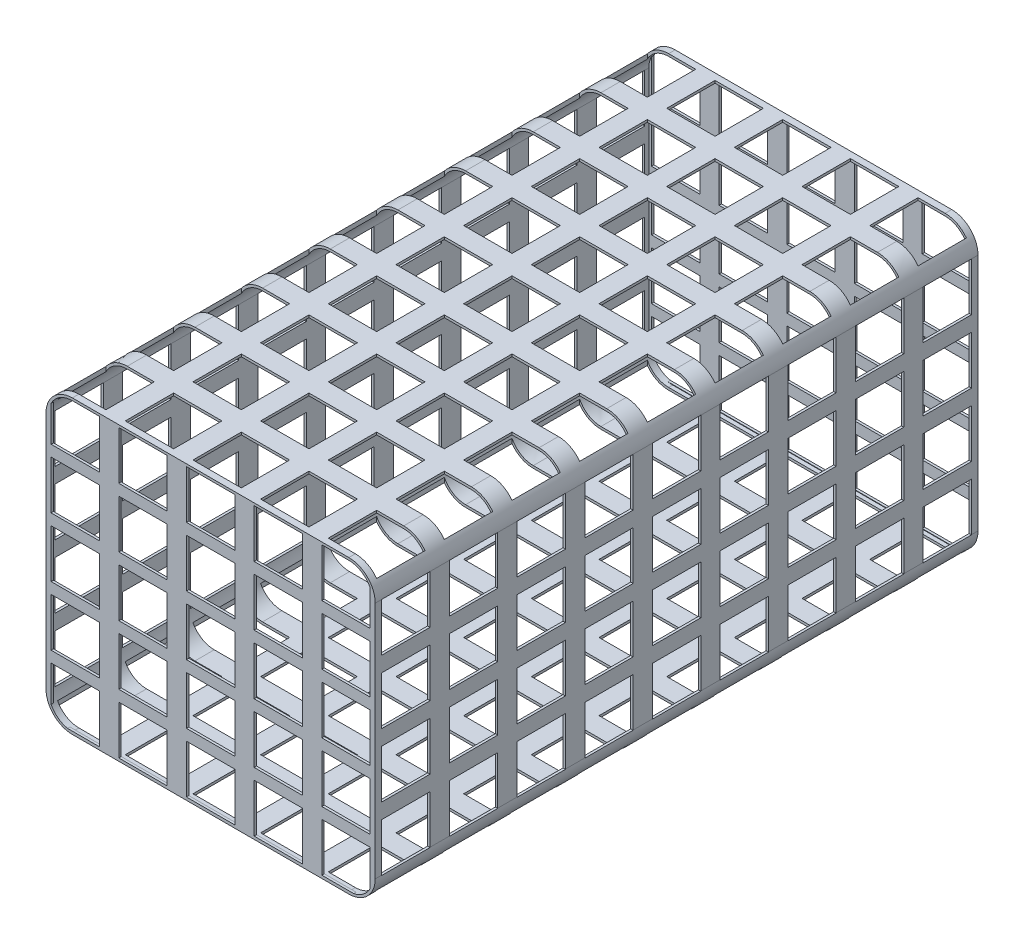
SolidWorks part; units mm, degrees
ref_plane "Front Plane" through (0, 0, 0) normal (0, 0, 1) x (1, 0, 0)
ref_plane "Top Plane" through (0, 0, 0) normal (0, 1, 0) x (1, 0, 0)
ref_plane "Right Plane" through (0, 0, 0) normal (1, 0, 0) x (0, 0, -1)
sketch "Sketch1" plane through (0, 0, 0) normal (0, 0, 1) x (1, 0, 0)
  line L0 (-72.644, 77.851) -> (72.644, 77.851)
  line L1 (-72.644, -76.581) -> (72.644, -76.581)
  line L2 (-86.487, -62.738) -> (-86.487, 62.738)
  line L3 (-72.644, 76.581) -> (72.644, 76.581)
  line L4 (86.487, -62.738) -> (86.487, 62.738)
  line L5 (-86.487, -76.581) -> (86.487, 76.581) construction
  line L6 (-86.487, 76.581) -> (86.487, -76.581) construction
  line L7 (87.757, -62.738) -> (87.757, 62.738)
  line L8 (-72.644, -77.851) -> (72.644, -77.851)
  line L9 (-87.757, -62.738) -> (-87.757, 62.738)
  arc A0 (86.487, 62.738) -> (72.644, 76.581) centre (72.644, 62.738) ccw
  arc A1 (86.487, -62.738) -> (72.644, -76.581) centre (72.644, -62.738) cw
  arc A2 (-72.644, -76.581) -> (-86.487, -62.738) centre (-72.644, -62.738) cw
  arc A3 (-86.487, 62.738) -> (-72.644, 76.581) centre (-72.644, 62.738) cw
  arc A4 (87.757, 62.738) -> (72.644, 77.851) centre (72.644, 62.738) ccw
  arc A5 (87.757, -62.738) -> (72.644, -77.851) centre (72.644, -62.738) cw
  arc A6 (-72.644, -77.851) -> (-87.757, -62.738) centre (-72.644, -62.738) cw
  arc A7 (-87.757, 62.738) -> (-72.644, 77.851) centre (-72.644, 62.738) cw
  point P0 (0, 0)
  dimension "D3" = 13.843
  dimension "D1" = 172.974
  dimension "D2" = 153.162
  dimension "D4" = 1.27
extrude "Boss-Extrude2" add sketch "Sketch1" along normal mid plane 316.738 contours A3 L2 A2 L1 A1 L4 A0 L3 | A3 L2 A2 L1 A1 L4 A0 L3 region at (0, 0, 0)
shell "Shell1" thickness 1.27
sketch "Sketch4" plane through (0, 76.581, 0) normal (0, 1, 0) x (1, 0, 0)
  line L0 (48.26, -12.7) -> (48.26, 12.7)
  line L1 (12.7, -12.7) -> (-12.7, -12.7)
  line L2 (12.7, -12.7) -> (12.7, 12.7)
  line L3 (12.7, 12.7) -> (-12.7, 12.7)
  line L4 (-12.7, -12.7) -> (-12.7, 12.7)
  line L5 (12.7, -12.7) -> (-12.7, 12.7) construction
  line L6 (12.7, 12.7) -> (-12.7, -12.7) construction
  line L7 (48.26, -12.7) -> (22.86, -12.7)
  line L8 (22.86, -12.7) -> (22.86, 12.7)
  line L9 (48.26, 12.7) -> (22.86, 12.7)
  line L10 (83.82, -12.7) -> (83.82, 12.7)
  line L11 (83.82, -12.7) -> (58.42, -12.7)
  line L12 (58.42, -12.7) -> (58.42, 12.7)
  line L13 (83.82, 12.7) -> (58.42, 12.7)
  line L14 (48.26, -48.26) -> (48.26, -22.86)
  line L15 (48.26, -48.26) -> (22.86, -48.26)
  line L16 (22.86, -48.26) -> (22.86, -22.86)
  line L17 (48.26, -22.86) -> (22.86, -22.86)
  line L18 (83.82, -48.26) -> (83.82, -22.86)
  line L19 (83.82, -48.26) -> (58.42, -48.26)
  line L20 (58.42, -48.26) -> (58.42, -22.86)
  line L21 (83.82, -22.86) -> (58.42, -22.86)
  line L22 (48.26, -83.82) -> (48.26, -58.42)
  line L23 (48.26, -83.82) -> (22.86, -83.82)
  line L24 (22.86, -83.82) -> (22.86, -58.42)
  line L25 (48.26, -58.42) -> (22.86, -58.42)
  line L26 (83.82, -83.82) -> (83.82, -58.42)
  line L27 (83.82, -83.82) -> (58.42, -83.82)
  line L28 (58.42, -83.82) -> (58.42, -58.42)
  line L29 (83.82, -58.42) -> (58.42, -58.42)
  line L30 (48.26, -119.38) -> (48.26, -93.98)
  line L31 (48.26, -119.38) -> (22.86, -119.38)
  line L32 (22.86, -119.38) -> (22.86, -93.98)
  line L33 (48.26, -93.98) -> (22.86, -93.98)
  line L34 (83.82, -119.38) -> (83.82, -93.98)
  line L35 (83.82, -119.38) -> (58.42, -119.38)
  line L36 (58.42, -119.38) -> (58.42, -93.98)
  line L37 (83.82, -93.98) -> (58.42, -93.98)
  line L38 (48.26, -154.94) -> (48.26, -129.54)
  line L39 (48.26, -154.94) -> (22.86, -154.94)
  line L40 (22.86, -154.94) -> (22.86, -129.54)
  line L41 (48.26, -129.54) -> (22.86, -129.54)
  line L42 (83.82, -154.94) -> (83.82, -129.54)
  line L43 (83.82, -154.94) -> (58.42, -154.94)
  line L44 (58.42, -154.94) -> (58.42, -129.54)
  line L45 (83.82, -129.54) -> (58.42, -129.54)
  line L46 (12.7, -48.26) -> (12.7, -22.86)
  line L47 (12.7, -48.26) -> (-12.7, -48.26)
  line L48 (-12.7, -48.26) -> (-12.7, -22.86)
  line L49 (12.7, -22.86) -> (-12.7, -22.86)
  line L50 (12.7, -83.82) -> (12.7, -58.42)
  line L51 (12.7, -83.82) -> (-12.7, -83.82)
  line L52 (-12.7, -83.82) -> (-12.7, -58.42)
  line L53 (12.7, -58.42) -> (-12.7, -58.42)
  line L54 (12.7, -119.38) -> (12.7, -93.98)
  line L55 (12.7, -119.38) -> (-12.7, -119.38)
  line L56 (-12.7, -119.38) -> (-12.7, -93.98)
  line L57 (12.7, -93.98) -> (-12.7, -93.98)
  line L58 (12.7, -154.94) -> (12.7, -129.54)
  line L59 (12.7, -154.94) -> (-12.7, -154.94)
  line L60 (-12.7, -154.94) -> (-12.7, -129.54)
  line L61 (12.7, -129.54) -> (-12.7, -129.54)
  point P0 (0, 0)
  dimension "D1" = 25.4
  dimension "D2" = 25.4
  dimension "D3" = 3
  dimension "D4" = 5
extrude "Cut-Extrude1" cut sketch "Sketch4" against normal through all
mirror "Mirror1" about plane through (0, 0, 0) normal (0, 0, 1) of "Cut-Extrude1"
mirror "Mirror2" about plane through (0, 0, 0) normal (1, 0, 0) of "Mirror1"
sketch "Sketch5" plane through (86.487, 0, 0) normal (1, 0, 0) x (0, 0, -1)
  line L1 (-154.94, 37.338) -> (-129.54, 37.338)
  line L2 (-154.94, 37.338) -> (-154.94, 62.738)
  line L3 (-154.94, 62.738) -> (-129.54, 62.738)
  line L4 (-129.54, 37.338) -> (-129.54, 62.738)
  line L5 (-154.94, 70.9066) -> (-154.94, 76.581) construction
  line L6 (-129.54, 76.581) -> (-129.54, 70.9066) construction
  line L7 (-158.369, 62.738) -> (158.369, 62.738) construction
  dimension "D1" = 25.4
extrude "Cut-Extrude3" cut sketch "Sketch5" against normal through all
pattern_linear "LPattern1" count 4 spacing 33.401 along (0, -1, 0) count 9 spacing 35.56 along (0, 0, -1) of "Cut-Extrude3"
sketch "Sketch6" plane through (0, 0, 158.369) normal (0, 0, 1) x (1, 0, 0)
  line L0 (-72.644, 76.581) -> (72.644, 76.581) construction
  line L1 (-12.7, 49.911) -> (12.7, 49.911)
  line L2 (-12.7, 49.911) -> (-12.7, 75.311)
  line L3 (-12.7, 75.311) -> (12.7, 75.311)
  line L4 (12.7, 49.911) -> (12.7, 75.311)
  line L5 (-12.7, 49.911) -> (12.7, 75.311) construction
  line L6 (-12.7, 75.311) -> (12.7, 49.911) construction
  point P0 (0, 62.611)
  dimension "D1" = 25.4
  dimension "D2" = 25.4
  dimension "D3" = 1.27
extrude "Cut-Extrude4" cut sketch "Sketch6" against normal through all
pattern_linear "LPattern2" count 5 spacing 31.242 along (0, -1, 0) of "Cut-Extrude4"
pattern_linear "LPattern3" count 2 spacing 35.56 along (-1, 0, 0) count 2 spacing 35.56 along (1, 0, 0) of "LPattern2"
sketch "Sketch7" plane through (0, 0, 158.369) normal (0, 0, 1) x (1, 0, 0)
  line L0 (48.26, -12.573) -> (48.26, 12.827) construction
  line L1 (58.42, 12.827) -> (83.82, 12.827)
  line L2 (58.42, 12.827) -> (58.42, -12.573)
  line L3 (58.42, -12.573) -> (83.82, -12.573)
  line L4 (83.82, 12.827) -> (83.82, -12.573)
  line L5 (48.26, 12.827) -> (22.86, 12.827) construction
  line L6 (83.82, 44.069) -> (83.82, 18.669)
  line L7 (58.42, 44.069) -> (58.42, 18.669)
  line L8 (58.42, 44.069) -> (83.82, 44.069)
  line L9 (58.42, 18.669) -> (83.82, 18.669)
  line L10 (58.42, 75.311) -> (83.82, 75.311)
  line L11 (83.82, 75.311) -> (83.82, 49.911)
  line L12 (58.42, 49.911) -> (83.82, 49.911)
  line L13 (58.42, 75.311) -> (58.42, 49.911)
  line L14 (58.42, -43.815) -> (83.82, -43.815)
  line L15 (83.82, -18.415) -> (83.82, -43.815)
  line L16 (58.42, -18.415) -> (83.82, -18.415)
  line L17 (58.42, -18.415) -> (58.42, -43.815)
  line L18 (83.82, -49.657) -> (83.82, -75.057)
  line L19 (58.42, -49.657) -> (83.82, -49.657)
  line L20 (58.42, -75.057) -> (83.82, -75.057)
  line L21 (58.42, -49.657) -> (58.42, -75.057)
  line L22 (22.86, 49.911) -> (48.26, 49.911) construction
  line L23 (48.26, 44.069) -> (22.86, 44.069) construction
  line L24 (48.26, -18.415) -> (22.86, -18.415) construction
  line L25 (48.26, -49.657) -> (22.86, -49.657) construction
  arc A2 (85.217, 62.738) -> (72.644, 75.311) centre (72.644, 62.738) ccw
  arc A3 (85.217, 62.738) -> (72.644, 75.311) centre (72.644, 62.738) ccw
  arc A5 (72.644, -75.311) -> (85.217, -62.738) centre (72.644, -62.738) ccw
  arc A6 (72.644, -75.311) -> (85.217, -62.738) centre (72.644, -62.738) ccw
  dimension "D1" = 10.16
  dimension "D2" = 25.4
  dimension "D3" = 25.4
  dimension "D4" = 25.4
  dimension "D5" = 25.4
  dimension "D6" = 25.4
  dimension "D7" = 25.4
  dimension "D8" = 1.27
  dimension "D9" = 1.27
extrude "Cut-Extrude5" cut sketch "Sketch7" against normal through all contours L11 A3 L10 L13 L12 | L7 L9 L6 L8 | L4 L1 L2 L3 | L16 L17 L14 L15 | L20 A6 L18 L19 L21 region at (71.12, 0.127, 158.369) region at (71.12, 31.369, 158.369) region at (70.7677, 62.2333, 158.369) region at (71.12, -31.115, 158.369) region at (70.7997, -62.0214, 158.369)
mirror "Mirror3" about plane through (0, 0, 0) normal (1, 0, 0) of "Cut-Extrude5"
